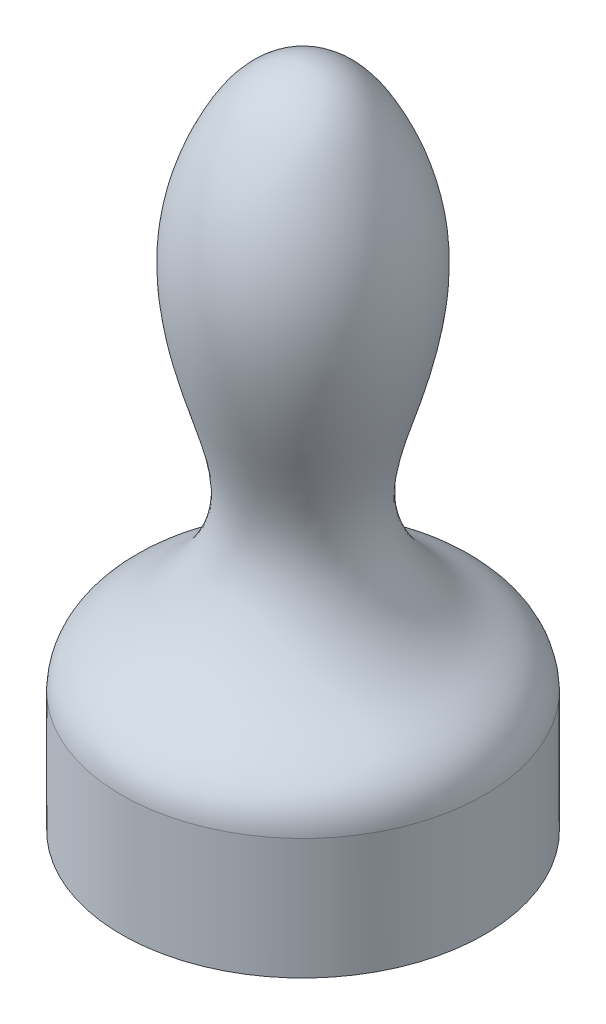
SolidWorks part; units mm, degrees
ref_plane "Alzado" through (0, 0, 0) normal (0, 0, 1) x (1, 0, 0)
ref_plane "Planta" through (0, 0, 0) normal (0, 1, 0) x (1, 0, 0)
ref_plane "Vista lateral" through (0, 0, 0) normal (1, 0, 0) x (0, 0, -1)
sketch "Croquis1" plane through (0, 0, 0) normal (0, 0, 1) x (1, 0, 0)
  line L0 (-12, 0) -> (-12, 5)
  line L1 (-12, 5) -> (0, 5)
  line L2 (0, 5) -> (0, 55)
  line L3 (-12, 0) -> (-15, 0)
  line L4 (-15, 0) -> (-15, 10)
  spline S0 degree 3 poles (0, 55) (-3.1808, 54.8692) (-6.8021, 49.9878) (-9.2969, 41.327) (-7.4603, 32.1649) (-3.9208, 22.7937) (-9.4071, 14.8728) (-14.8388, 12.976) (-15, 10) knots 0 0 0 0 0.153338 0.314153 0.514829 0.684692 0.859563 1 1 1 1
  dimension "D1" = 50
  dimension "D2" = 15
  dimension "D3" = 3
  dimension "D4" = 10
  dimension "D5" = 5
revolve "Revolución1" add sketch "Croquis1" angle 360 about L2
thread "Rosca1" pitch 1.5 method extrude profile "Perfil de rosca1" start angle 0, offset 1.5, length 0, pitch 1.5, diameter 24
ref_plane "Plano1" through (12, -1.5, 0) normal (0, 0, 1) x (1, 0, 0)
sketch "Perfil de rosca1" plane through (12, -1.5, 0) normal (0, 0, 1) x (1, 0, 0)
  line L0 (0, 0) -> (0, 1.5) construction
  line L11 (0, 0) -> (0, 1.3125)
  line L12 (0, 1.3125) -> (-0.8119, 0.8437)
  line L13 (-0.8119, 0.8437) -> (-0.8119, 0.4687)
  line L15 (-0.8119, 0.4687) -> (0, 0)
  line L17 (-0.8119, 0.6562) -> (0, 0.6562) construction
  point P2 (0, 0)
  dimension "Pitch" = 1.5
  dimension "Profile_Angle" = 60
  dimension "Profile_Land" = 0.375
  dimension "Profile_Height" = 0.8119
sketch "Croquis3" plane through (0, 0, 0) normal (0, -1, 0) x (1, 0, 0)
  circle A0 centre (0, 0) radius 15
extrude "Cortar-Extruir1" cut sketch "Croquis3" along normal blind 10
